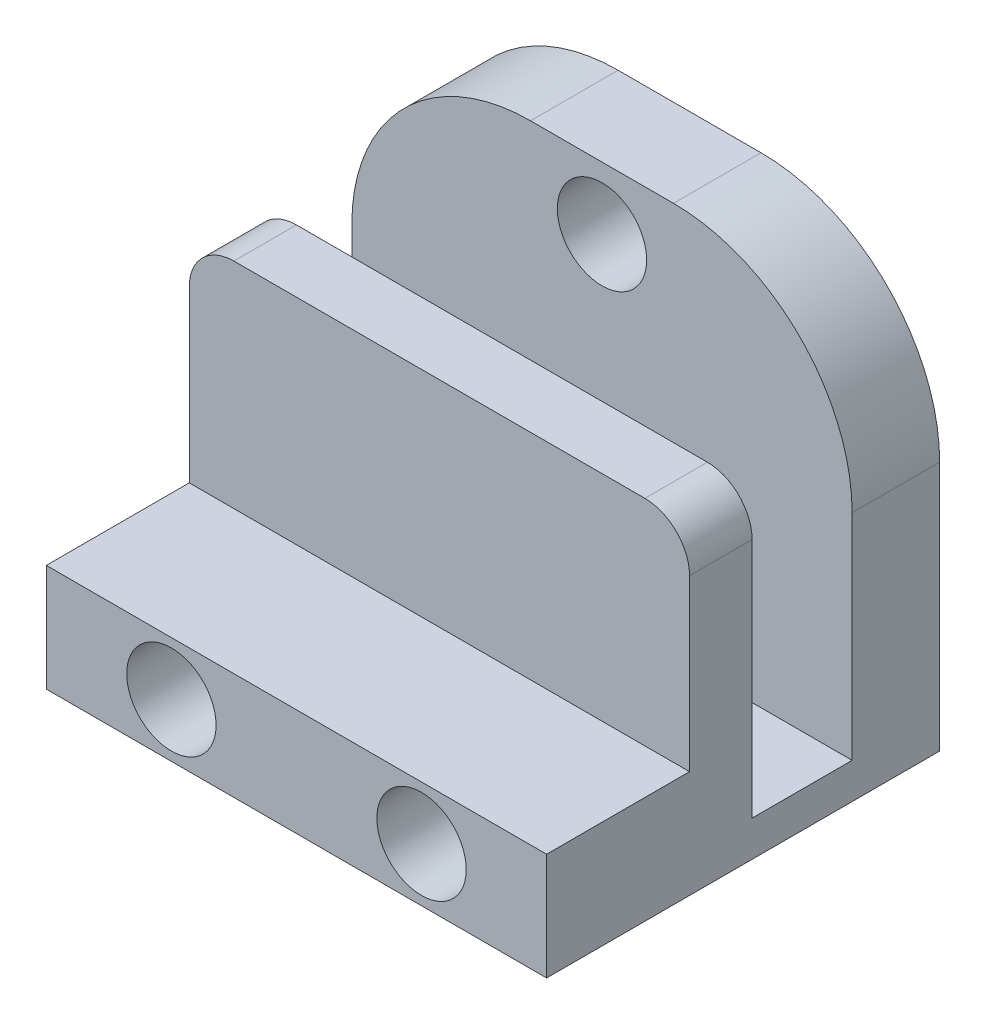
SolidWorks part; units mm, degrees
ref_plane "Front" through (0, 0, 0) normal (0, 0, 1) x (1, 0, 0)
ref_plane "Top" through (0, 0, 0) normal (0, 1, 0) x (1, 0, 0)
ref_plane "Right" through (0, 0, 0) normal (1, 0, 0) x (0, 0, -1)
sketch "Sketch1" plane through (0, 0, 0) normal (0, 1, 0) x (1, 0, 0)
  line L0 (0, 0) -> (0, 25.4)
  line L1 (0, 25.4) -> (35.56, 25.4)
  line L2 (35.56, 25.4) -> (35.56, 0)
  line L3 (31.75, 0) -> (22.86, 0)
  line L4 (22.86, 0) -> (22.86, 7.62)
  line L6 (12.7, 7.62) -> (12.7, 0)
  line L7 (12.7, 0) -> (3.81, 0)
  line L8 (3.81, 0) -> (3.81, -8.89)
  line L9 (3.81, -8.89) -> (0, -8.89)
  line L10 (0, -8.89) -> (0, 0)
  line L11 (0, 0) -> (0, -8.89)
  line L12 (31.75, 0) -> (31.75, -8.89)
  line L13 (31.75, -8.89) -> (35.56, -8.89)
  line L14 (35.56, -8.89) -> (35.56, 0)
  line L15 (12.7, 7.62) -> (22.86, 7.62)
  dimension "D1" = 8.89
  dimension "D2" = 7.62
  dimension "D3" = 25.4
  dimension "D4" = 10.16
  dimension "D5" = 35.56
extrude "Boss-Extrude1" add sketch "Sketch1" along normal blind 7.62 contours L6 L15 L4 L3 L12 L13 L14 L2 L1 L0 L10 L9 L8 L7 region at (17.78, 0, -12.1705)
sketch "Sketch2" plane through (0, 7.62, 0) normal (0, 1, 0) x (1, 0, 0)
  line L0 (0, 7.62) -> (35.56, 7.62)
  line L2 (35.56, -8.89) -> (35.56, 25.4) construction
  line L3 (0, -8.89) -> (0, 25.4) construction
  line L4 (0, 25.4) -> (35.56, 25.4) construction
  line L5 (0, 7.62) -> (0, 25.4)
  line L6 (35.56, 7.62) -> (35.56, 25.4)
  line L7 (0, 25.4) -> (35.56, 25.4)
  line L8 (12.7, 7.62) -> (22.86, 7.62) construction
  point P3 (17.78, 7.62)
extrude "Boss-Extrude2" add sketch "Sketch2" along normal blind 22.86
sketch "Sketch4" plane through (0, 30.48, 0) normal (0, 1, 0) x (1, 0, 0)
  line L0 (0, 19.177) -> (35.56, 19.177)
  line L1 (0, 25.4) -> (0, 7.62) construction
  line L2 (35.56, 7.62) -> (35.56, 25.4) construction
  line L3 (0, 12.065) -> (35.56, 12.065)
  line L4 (0, 19.177) -> (0, 12.065)
  line L5 (35.56, 19.177) -> (35.56, 12.065)
  line L6 (0, 7.62) -> (35.56, 7.62) construction
  dimension "D1" = 7.112
  dimension "D2" = 4.445
extrude "Cut-Extrude2" cut sketch "Sketch4" against normal blind 27.94
sketch "Sketch5" plane through (0, 30.48, 0) normal (0, 1, 0) x (1, 0, 0)
  line L0 (35.56, 7.62) -> (35.56, 12.065) construction
  line L1 (0, 7.62) -> (35.56, 7.62) construction
  line L2 (0, 12.065) -> (0, 7.62) construction
  line L3 (0, 12.065) -> (35.56, 12.065) construction
  line L4 (35.56, 7.62) -> (35.56, 12.065)
  line L5 (0, 7.62) -> (35.56, 7.62)
  line L6 (0, 12.065) -> (0, 7.62)
  line L7 (0, 12.065) -> (35.56, 12.065)
extrude "Cut-Extrude3" cut sketch "Sketch5" against normal blind 7.62
sketch "Sketch6" plane through (0, 0, -25.4) normal (0, 0, -1) x (-1, 0, 0)
  line L0 (-17.78, 30.48) -> (-17.78, 20.6523) construction
  line L1 (-35.56, 30.48) -> (0, 30.48) construction
  circle A0 centre (-17.78, 26.035) radius 3.175
  dimension "D1" = 6.35
  dimension "D2" = 4.445
extrude "Cut-Extrude4" cut sketch "Sketch6" against normal blind 6.35
sketch "Sketch7" plane through (0, 0, 0) normal (0, 0, 1) x (1, 0, 0)
  line L0 (27.305, 7.62) -> (27.305, 3.81) construction
  line L1 (31.75, 7.62) -> (22.86, 7.62) construction
  line L2 (27.305, 3.81) -> (22.86, 3.81) construction
  line L3 (22.86, 7.62) -> (22.86, 0) construction
  line L4 (17.78, 0) -> (17.78, 9.9153) construction
  line L5 (12.7, 0) -> (22.86, 0) construction
  line L6 (8.255, 3.81) -> (12.7, 3.81) construction
  line L7 (8.255, 7.62) -> (8.255, 3.81) construction
  circle A0 centre (27.305, 3.81) radius 3.175
  circle A1 centre (8.255, 3.81) radius 3.175
  dimension "D1" = 6.35
extrude "Cut-Extrude5" [suppressed] cut sketch "Sketch7" against normal blind 9.525
fillet "Fillet1" radius 12.7 2 edges at (0, 30.48, -22.2885) (35.56, 30.48, -22.2885)
fillet "Fillet2" radius 3.175 2 edges at (0, 22.86, -9.8425) (35.56, 22.86, -9.8425)
sketch "Sketch8" plane through (0, 7.62, 0) normal (0, 1, 0) x (1, 0, 0)
  line L0 (12.7, 7.62) -> (22.86, 7.62)
  line L1 (22.86, 7.62) -> (22.86, 0)
  line L2 (22.86, 0) -> (31.75, 0)
  line L3 (31.75, 0) -> (31.75, -8.89)
  line L4 (31.75, -8.89) -> (3.81, -8.89)
  line L5 (3.81, -8.89) -> (3.81, 0)
  line L6 (3.81, 0) -> (12.7, 0)
  line L7 (12.7, 0) -> (12.7, 7.62)
extrude "Boss-Extrude3" add sketch "Sketch8" against normal up to surface (7.62 mm away) up to face at (17.78, 0, -2.54)
sketch "Sketch9" plane through (0, 0, 0) normal (0, -1, 0) x (1, 0, 0)
  line L0 (0, 2.54) -> (35.56, 2.54)
  line L1 (0, 8.89) -> (0, -25.4) construction
  line L2 (35.56, 8.89) -> (35.56, -25.4) construction
  line L3 (35.56, 8.89) -> (0, 8.89) construction
  line L4 (0, 8.89) -> (0, 2.54)
  line L5 (35.56, 8.89) -> (35.56, 2.54)
  line L6 (35.56, 8.89) -> (0, 8.89)
  dimension "D1" = 6.35
extrude "Boss-Extrude4" [suppressed] add sketch "Sketch9" along normal blind 25.4
sketch "Sketch10" [suppressed] plane through (0, 0, 8.89) normal (0, 0, 1) x (1, 0, 0)
  line L0 (0, 0) -> (35.56, 0) construction
  line L1 (35.56, 7.62) -> (35.56, -25.4) construction
  line L2 (17.78, 0) -> (17.78, -25.4) construction
  line L3 (35.56, -25.4) -> (0, -25.4) construction
  line L4 (5.08, -12.7) -> (30.48, -12.7) construction
  circle A0 centre (5.08, -12.7) radius 2.5781
  circle A1 centre (17.78, -12.7) radius 1.5827
  circle A2 centre (30.48, -12.7) radius 1.2748
  point P12 (17.78, -12.7)
  point P13 (17.78, -12.7)
  dimension "D2" = 5.1562
  dimension "D1" = 25.4
sketch "Sketch11" plane through (0, 7.62, 0) normal (0, 1, 0) x (1, 0, 0)
  line L0 (0, -2.54) -> (35.56, -2.54)
  line L1 (0, -8.89) -> (0, 7.62) construction
  line L2 (35.56, -8.89) -> (35.56, 7.62) construction
  line L3 (0, -8.89) -> (35.56, -8.89) construction
  line L4 (35.56, -8.89) -> (35.56, -2.54)
  line L5 (0, -8.89) -> (35.56, -8.89)
  line L6 (0, -8.89) -> (0, -2.54)
  dimension "D1" = 6.35
extrude "Cut-Extrude6" cut sketch "Sketch11" against normal through all
sketch "Sketch12" plane through (0, 0, 2.54) normal (0, 0, 1) x (1, 0, 0)
  line L0 (17.78, 7.62) -> (17.78, 0) construction
  line L1 (35.56, 7.62) -> (0, 7.62) construction
  line L2 (35.56, 0) -> (0, 0) construction
  line L3 (17.78, 3.81) -> (0, 3.81) construction
  line L4 (0, 0) -> (0, 7.62) construction
  line L5 (17.78, 3.81) -> (35.56, 3.81) construction
  line L6 (35.56, 0) -> (35.56, 7.62) construction
  circle A0 centre (8.89, 3.81) radius 3.175
  circle A1 centre (26.67, 3.81) radius 3.175
  dimension "D1" = 6.35
extrude "Cut-Extrude7" cut sketch "Sketch12" against normal blind 7.62
